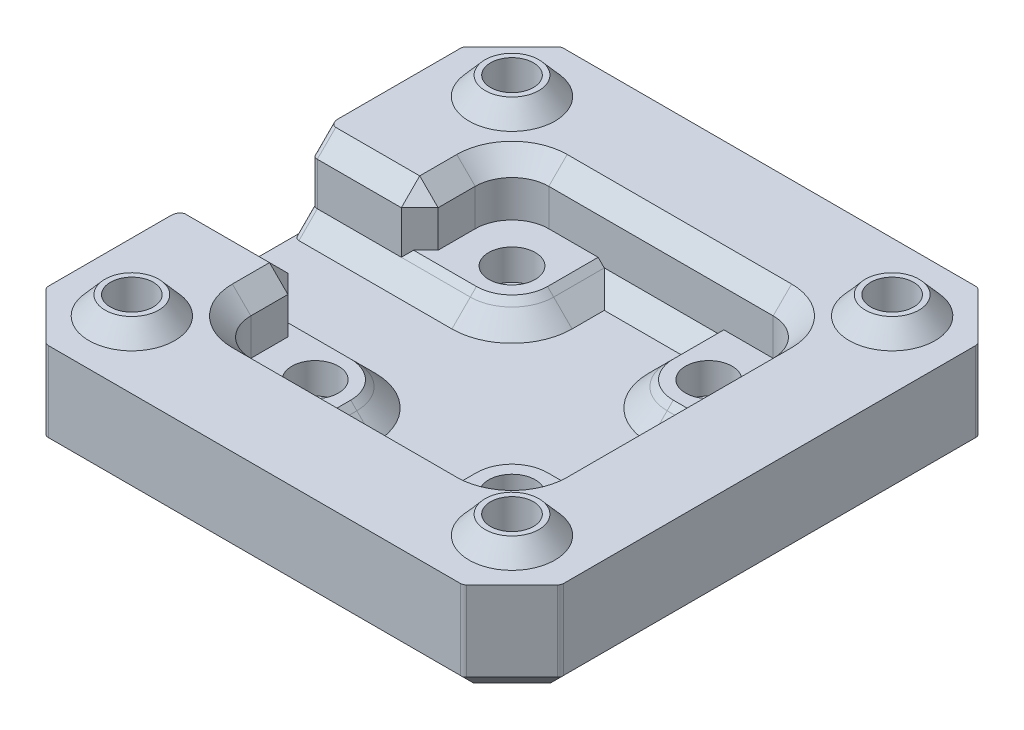
SolidWorks part; units mm, degrees
material "ABS"
ref_plane "Front Plane" through (0, 0, 0) normal (0, 0, 1) x (1, 0, 0)
ref_plane "Top Plane" through (0, 0, 0) normal (0, 1, 0) x (1, 0, 0)
ref_plane "Right Plane" through (0, 0, 0) normal (1, 0, 0) x (0, 0, -1)
sketch "Sketch1" plane through (0, 0, 0) normal (0, 1, 0) x (1, 0, 0)
  line L8 (-17, 21) -> (-21, 17)
  line L9 (17, -21) -> (-17, -21)
  line L10 (21, -17) -> (21, 17)
  line L11 (17, 21) -> (-17, 21)
  line L12 (-21, -17) -> (-21, 17)
  line L13 (21, 17) -> (17, 21)
  line L14 (21, -17) -> (17, -21)
  line L15 (-17, -21) -> (-21, -17)
  point P0 (21, -21)
  point P1 (-21, 21)
  point P2 (21, 21)
  point P3 (-21, -21)
  point P12 (21, 0)
  point P14 (0, 21)
  dimension "D1" = 42
extrude "Base Extrude" add sketch "Sketch1" along normal blind 8
chamfer "Back Chamfer" distance 1.5 angle 45 8 edges at (-19, 0, -19) (-21, 0, 0) (-19, 0, 19) (0, 0, 21) (0, 0, -21) (19, 0, -19) (21, 0, 0) (19, 0, 19)
sketch "Sketch2" plane through (0, 8, 0) normal (0, 1, 0) x (1, 0, 0)
  circle A0 centre (-15.5, 15.5) radius 1.75
  circle A1 centre (15.5, 15.5) radius 1.75
  circle A2 centre (15.5, -15.5) radius 1.75
  circle A3 centre (-15.5, -15.5) radius 1.75
  point P12 (0, 0)
  dimension "D3" = 3.5
  dimension "D1" = 15.5
  dimension "D2" = 15.5
  dimension "D4" = 4
extrude "Motor Screw Hole2" cut sketch "Sketch2" against normal through all
ref_plane "Motor Screw Hole Plane" through (0, 0, 15.5) normal (0, 0, 1) x (1, 0, 0)
sketch "Sketch6" plane through (0, 0, 15.5) normal (0, 0, 1) x (1, 0, 0)
  line L0 (-15.5, -992) -> (-15.5, 49008) construction
  line L1 (-13.75, 8) -> (-17.25, 8) construction
  line L2 (-18.25, 0) -> (-17, 2)
  line L3 (-15.5, 0) -> (-18.25, 0)
  line L4 (-17.25, 0) -> (-13.75, 0) construction
  line L8 (-15.5, 2) -> (-15.5, 0)
  line L10 (-17, 2) -> (-15.5, 2)
  point P5 (-15.5, 8)
  point P7 (-15.5, 2)
  dimension "D1" = 5.5
  dimension "D2" = 2
  dimension "D3" = 3
revolve "Motor Screw Entry Chamfer" cut sketch "Sketch6" angle 360 about L0
sketch "Sketch11" plane through (0, 0, 15.5) normal (0, 0, 1) x (1, 0, 0)
  line L0 (-15.5, -992) -> (-15.5, 49008) construction
  line L1 (-13.75, 8) -> (-17.25, 8) construction
  line L2 (-17.25, 8) -> (-17.25, 9.5)
  line L3 (-17.6875, 9.5) -> (-19, 8)
  line L4 (-17, 8) -> (-21, 8) construction
  line L5 (-19, 8) -> (-17.25, 8)
  line L6 (-17.25, 9.5) -> (-17.6875, 9.5)
  line L7 (-17.25, 9.5) -> (-17.25, 10) construction
  line L8 (-17.25, 10) -> (-17.6875, 9.5) construction
  point P5 (-15.5, 8)
  dimension "D1" = 2
  dimension "D2" = 7
  dimension "D3" = 0.5
revolve "Motor Screw Alignment Revolve" add sketch "Sketch11" angle 360 about L0
mirror "Motor Screw Pattern" about plane through (0, 0, 0) normal (1, 0, 0) of "Motor Screw Alignment Revolve", "Motor Screw Entry Chamfer" second plane through (0, 0, 0) second plane normal (0, 0, 1)
sketch "Sketch3" plane through (0, 8, 0) normal (0, 1, 0) x (1, 0, 0)
  line L1 (-9.15, -12.15) -> (9.15, -12.15)
  line L2 (-12.15, -9.15) -> (-12.15, 9.15)
  line L3 (-9.15, 12.15) -> (9.15, 12.15)
  line L4 (12.15, -9.15) -> (12.15, 9.15)
  line L5 (-12.15, -12.15) -> (12.15, 12.15) construction
  line L6 (-12.15, 12.15) -> (12.15, -12.15) construction
  arc A0 (-9.15, -12.15) -> (-12.15, -9.15) centre (-9.15, -9.15) cw
  arc A1 (9.15, -12.15) -> (12.15, -9.15) centre (9.15, -9.15) ccw
  arc A2 (9.15, 12.15) -> (12.15, 9.15) centre (9.15, 9.15) cw
  arc A3 (-12.15, 9.15) -> (-9.15, 12.15) centre (-9.15, 9.15) cw
  point P0 (0, 0)
  dimension "D2" = 3
  dimension "D1" = 24.3
extrude "Sensor Holder Cut" cut sketch "Sketch3" against normal blind 4.5
sketch "Sketch5" plane through (0, 3.5, 0) normal (0, 1, 0) x (1, 0, 0)
  circle A0 centre (-8.025, 8.025) radius 1.9
  circle A1 centre (8.025, 8.025) radius 1.9
  circle A2 centre (8.025, -8.025) radius 1.9
  circle A3 centre (-8.025, -8.025) radius 1.9
  point P12 (0, 0)
  dimension "D3" = 3.8
  dimension "D1" = 8.025
  dimension "D2" = 8.025
  dimension "D4" = 4
extrude "Sensor Holder Holes" cut sketch "Sketch5" against normal blind 2.5
sketch "Sketch8" plane through (0, 3.5, 0) normal (0, 1, 0) x (1, 0, 0)
  line L0 (-12.15, 4.625) -> (-8.025, 4.625)
  line L1 (-12.15, 9.15) -> (-12.15, -9.15) construction
  line L2 (-4.625, 8.025) -> (-4.625, 12.15)
  line L3 (9.15, 12.15) -> (-9.15, 12.15) construction
  line L4 (8.025, 4.625) -> (12.15, 4.625)
  line L5 (4.625, 12.15) -> (4.625, 8.025)
  line L6 (4.625, -8.025) -> (4.625, -12.15)
  line L7 (12.15, -4.625) -> (8.025, -4.625)
  line L8 (-8.025, -4.625) -> (-12.15, -4.625)
  line L9 (-4.625, -12.15) -> (-4.625, -8.025)
  line L10 (-12.15, 4.625) -> (-12.15, -4.625)
  line L11 (-4.625, -12.15) -> (4.625, -12.15)
  line L12 (12.15, -4.625) -> (12.15, 4.625)
  line L13 (4.625, 12.15) -> (-4.625, 12.15)
  circle A0 centre (-8.025, 8.025) radius 1.9 construction
  circle A1 centre (-8.025, 8.025) radius 1.9 construction
  arc A2 (-8.025, 4.625) -> (-4.625, 8.025) centre (-8.025, 8.025) ccw
  arc A3 (4.625, 8.025) -> (8.025, 4.625) centre (8.025, 8.025) ccw
  arc A4 (8.025, -4.625) -> (4.625, -8.025) centre (8.025, -8.025) ccw
  arc A5 (-4.625, -8.025) -> (-8.025, -4.625) centre (-8.025, -8.025) ccw
  point P30 (0, 0)
  dimension "D1" = 1.5
  dimension "D2" = 4
extrude "Wire Spacer Cut" cut sketch "Sketch8" against normal blind 2
sketch "Sketch9" plane through (0, 1.5, 0) normal (0, 1, 0) x (1, 0, 0)
  line L0 (-12.15, -4.625) -> (-8.025, -4.625) construction
  line L1 (-8.025, 4.625) -> (-21, 4.625)
  line L2 (-8.025, 4.625) -> (-8.025, -4.625)
  line L3 (-8.025, -4.625) -> (-21, -4.625)
  line L4 (-21, 4.625) -> (-21, -4.625)
  line L5 (-21, 17) -> (-21, -17) construction
extrude "Wire Output Cut" cut sketch "Sketch9" along normal through all
chamfer "Large Internal Chamfers" distance 1.5 angle 45 28 edges at (0, 1.5, 12.15) (4.625, 1.5, 10.0875) (10.0875, 1.5, 4.625) (5.6208, 1.5, 5.6208) (12.15, 1.5, 0) (10.0875, 1.5, -4.625) (5.6208, 1.5, -5.6208) (4.625, 1.5, -10.0875) (0, 1.5, -12.15) (-4.625, 1.5, 10.0875) (-5.6208, 1.5, 5.6208) (-14.5125, 1.5, 4.625) (-4.625, 1.5, -10.0875) (-5.6208, 1.5, -5.6208) (-14.5125, 1.5, -4.625) (-16.575, 8, 4.625) (-16.575, 8, -4.625) (-12.15, 8, 6.8875) (-11.2713, 8, 11.2713) (0, 8, 12.15) (11.2713, 8, 11.2713) (12.15, 8, 0) (-12.15, 8, -6.8875) (11.2713, 8, -11.2713) (-11.2713, 8, -11.2713) (0, 8, -12.15) (-12.15, 5.75, 4.625) (-12.15, 5.75, -4.625)
chamfer "Small Internal Chamfers" distance 0.5 angle 45 12 edges at (-10.8375, 3.5, 4.625) (-4.625, 3.5, 10.0875) (-5.6208, 3.5, 5.6208) (4.625, 3.5, 10.0875) (10.0875, 3.5, 4.625) (5.6208, 3.5, 5.6208) (10.0875, 3.5, -4.625) (4.625, 3.5, -10.0875) (5.6208, 3.5, -5.6208) (-4.625, 3.5, -10.0875) (-10.8375, 3.5, -4.625) (-5.6208, 3.5, -5.6208)
fillet "Exterier Edge Fillets" radius 0.5 14 edges at (-21, 7.25, 5.375) (-21, 7.25, -5.375) (-21, 4.75, -4.625) (-21, 2.25, -3.875) (-21, 2.25, 3.875) (-21, 4.75, 4.625) (21, 4.75, -17) (17, 4.75, -21) (-17, 4.75, -21) (-21, 4.75, -17) (-21, 4.75, 17) (-17, 4.75, 21) (17, 4.75, 21) (21, 4.75, 17)
